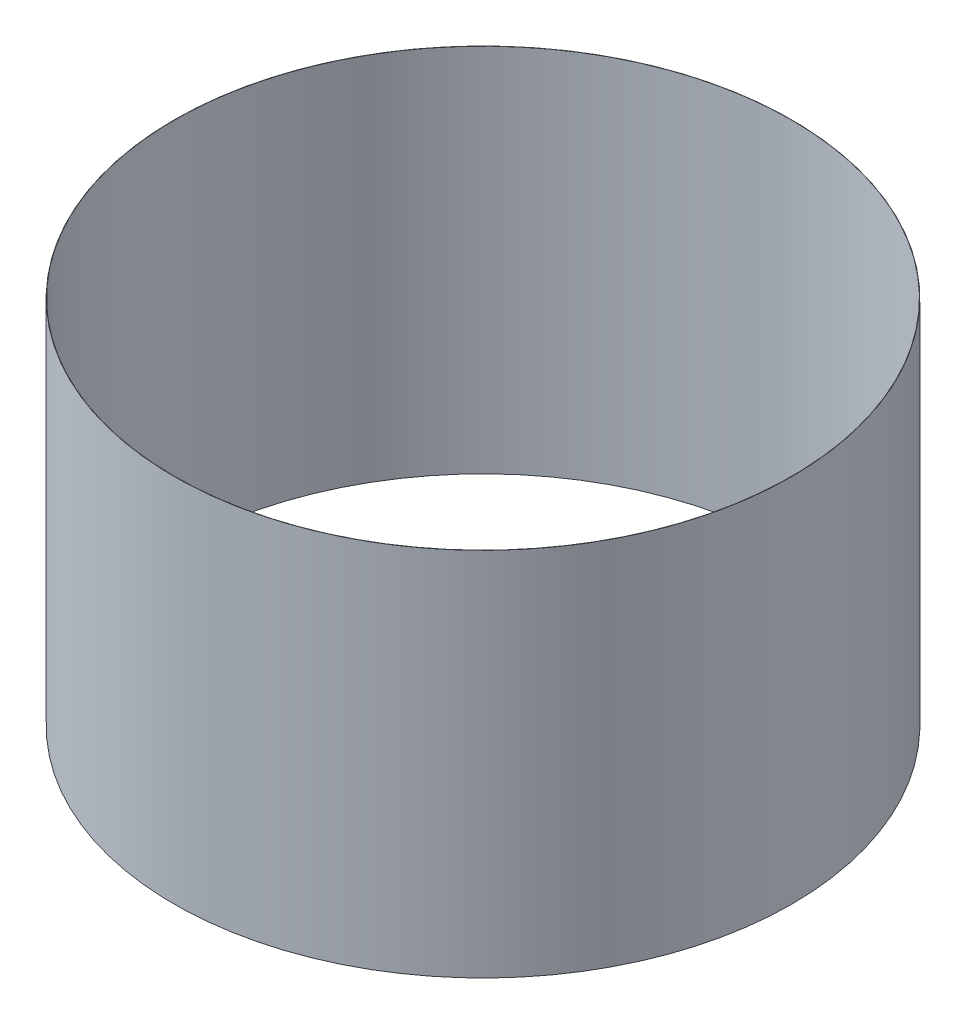
SolidWorks part; units mm, degrees
ref_plane "Front Plane" through (0, 0, 0) normal (0, 0, 1) x (1, 0, 0)
ref_plane "Top Plane" through (0, 0, 0) normal (0, 1, 0) x (1, 0, 0)
ref_plane "Right Plane" through (0, 0, 0) normal (1, 0, 0) x (0, 0, -1)
sketch "Sketch1" plane through (0, 0, 0) normal (0, 1, 0) x (1, 0, 0)
  circle A0 centre (0, 0) radius 125
  dimension "D1" = 250
extrude "Extrude-Thin1" add sketch "Sketch1" along normal blind 150 thin contours A0 thin type one direction wall 0.1
